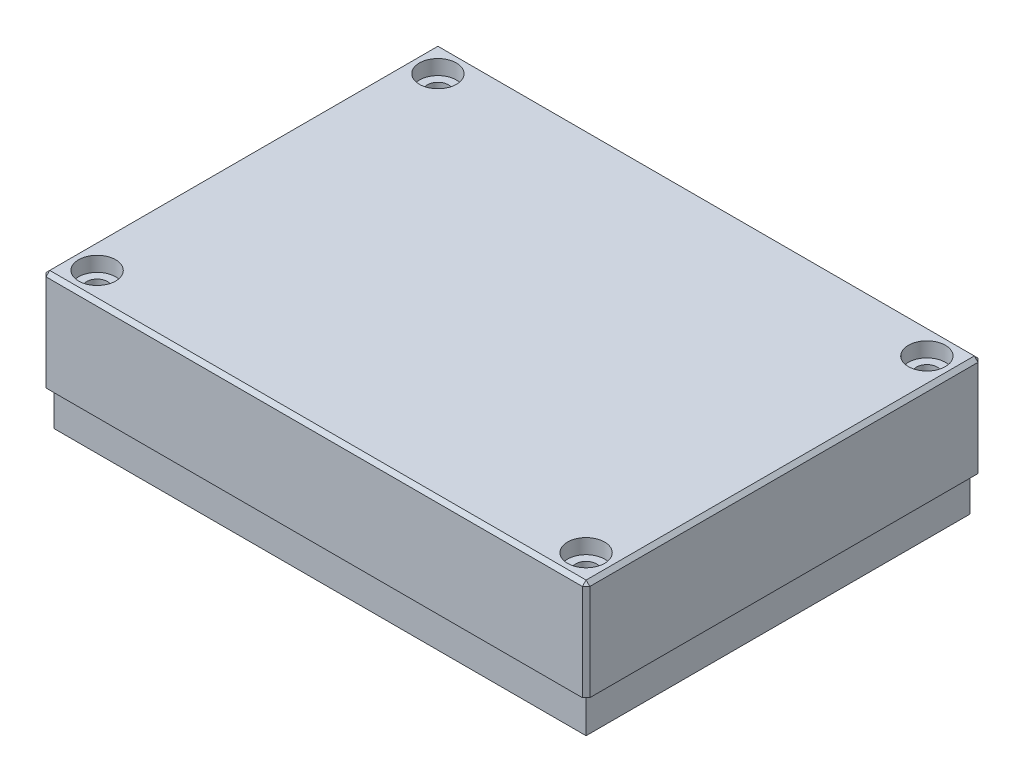
SolidWorks part; units mm, degrees
ref_plane "Спереди" through (0, 0, 0) normal (0, 0, 1) x (1, 0, 0)
ref_plane "Сверху" through (0, 0, 0) normal (0, 1, 0) x (1, 0, 0)
ref_plane "Справа" through (0, 0, 0) normal (1, 0, 0) x (0, 0, -1)
other "Configuration Table"
sketch "Эскиз1" plane through (0, 0, 0) normal (0, 1, 0) x (1, 0, 0)
  line L0 (-34.8, 24.8) -> (34.8, 24.8)
  line L1 (-35, -25) -> (35, -25) construction
  line L2 (-35, -25) -> (-35, 25) construction
  line L3 (-35, 25) -> (35, 25) construction
  line L4 (35, -25) -> (35, 25) construction
  line L5 (-35, -25) -> (35, 25) construction
  line L6 (-35, 25) -> (35, -25) construction
  line L7 (34.8, -24.8) -> (34.8, 24.8)
  line L8 (-34.8, -24.8) -> (34.8, -24.8)
  line L9 (-34.8, -24.8) -> (-34.8, 24.8)
  line L10 (-36.7, 26.7) -> (36.7, 26.7)
  line L11 (36.7, -26.7) -> (36.7, 26.7)
  line L12 (-36.7, -26.7) -> (36.7, -26.7)
  line L13 (-36.7, -26.7) -> (-36.7, 26.7)
  point P0 (0, 0)
  dimension "D1" = 70
  dimension "D2" = 50
  dimension "D3" = 0.2
  dimension "D4" = 1.9
extrude "Бобышка-Вытянуть1" add sketch "Эскиз1" against normal blind 17
sketch "Эскиз2" plane through (0, 0, 0) normal (0, 1, 0) x (1, 0, 0)
  line L1 (-36.7, 26.7) -> (36.7, 26.7)
  line L2 (-36.7, 26.7) -> (-36.7, -26.7)
  line L3 (-36.7, -26.7) -> (36.7, -26.7)
  line L4 (36.7, 26.7) -> (36.7, -26.7)
  line L5 (-36.7, 26.7) -> (36.7, -26.7) construction
  line L6 (-36.7, -26.7) -> (36.7, 26.7) construction
  point P4 (0, 0)
extrude "Бобышка-Вытянуть2" add sketch "Эскиз2" along normal blind 1.5
sketch "Эскиз3" plane through (0, 0, 0) normal (0, 1, 0) x (1, 0, 0)
  line L0 (-34.8, -24.8) -> (-34.8, 24.8) construction
  line L1 (-34.8, 24.8) -> (-30.3, 24.8)
  line L2 (-34.8, 24.8) -> (-34.8, 20.3)
  line L3 (-34.8, 20.3) -> (-30.3, 20.3)
  line L4 (-30.3, 24.8) -> (-30.3, 20.3)
  line L5 (-34.8, 24.8) -> (-30.3, 20.3) construction
  line L6 (-34.8, 20.3) -> (-30.3, 24.8) construction
  line L7 (-34.8, 24.8) -> (34.8, 24.8) construction
  line L8 (0, 0) -> (0, 17.8052) construction
  line L9 (0, 0) -> (16.7249, 0) construction
  line L10 (34.8, 20.3) -> (30.3, 24.8) construction
  line L11 (34.8, 24.8) -> (30.3, 20.3) construction
  line L12 (30.3, 24.8) -> (30.3, 20.3)
  line L13 (34.8, 20.3) -> (30.3, 20.3)
  line L14 (34.8, 24.8) -> (34.8, 20.3)
  line L15 (34.8, 24.8) -> (30.3, 24.8)
  line L16 (-34.8, -20.3) -> (-30.3, -24.8) construction
  line L17 (-34.8, -24.8) -> (-30.3, -20.3) construction
  line L18 (-30.3, -24.8) -> (-30.3, -20.3)
  line L19 (-34.8, -20.3) -> (-30.3, -20.3)
  line L20 (-34.8, -24.8) -> (-34.8, -20.3)
  line L21 (-34.8, -24.8) -> (-30.3, -24.8)
  line L22 (34.8, -24.8) -> (30.3, -20.3) construction
  line L23 (34.8, -20.3) -> (30.3, -24.8) construction
  line L24 (34.8, -24.8) -> (30.3, -24.8)
  line L25 (34.8, -24.8) -> (34.8, -20.3)
  line L26 (34.8, -20.3) -> (30.3, -20.3)
  line L27 (30.3, -24.8) -> (30.3, -20.3)
  point P4 (-32.55, 22.55)
  point P17 (32.55, 22.55)
  point P22 (-32.55, -22.55)
  point P27 (32.55, -22.55)
  dimension "D1" = 4.5
  dimension "D2" = 4.5
extrude "Бобышка-Вытянуть3" add sketch "Эскиз3" against normal through all
sketch "Эскиз9" plane through (0, 0, 0) normal (0, 1, 0) x (-1, 0, 0)
  circle A1 centre (-33, 23) radius 3.2527
  circle A2 centre (-33, -23) radius 3.2527
  circle A3 centre (33, -23) radius 3.2527
  circle A4 centre (33, 23) radius 3.2527
extrude "Бобышка-Вытянуть5" add sketch "Эскиз9" against normal blind 2
chamfer "Фаска1" distance 0.5 angle 45 8 edges at (0, 1.5, 26.7) (-36.7, -7.75, 26.7) (-36.7, 1.5, 0) (-36.7, -7.75, -26.7) (0, 1.5, -26.7) (36.7, -7.75, -26.7) (36.7, 1.5, 0) (36.7, -7.75, 26.7)
sketch "Эскиз6" plane through (0, -17, 0) normal (0, -1, 0) x (1, 0, 0)
  line L0 (36.7, 26.7) -> (36.7, -26.7) construction
  line L1 (-35.9, -25.9) -> (35.9, -25.9)
  line L2 (-35.9, -25.9) -> (-35.9, 25.9)
  line L3 (-35.9, 25.9) -> (35.9, 25.9)
  line L4 (35.9, -25.9) -> (35.9, 25.9)
  line L5 (-35.9, -25.9) -> (35.9, 25.9) construction
  line L6 (-35.9, 25.9) -> (35.9, -25.9) construction
  line L7 (-36.7, 26.7) -> (36.7, 26.7) construction
  point P0 (0, 0)
  dimension "D1" = 0.8
  dimension "D2" = 0.8
extrude "Вырез-Вытянуть3" cut sketch "Эскиз6" against normal blind 5 flip side to cut
sketch "Эскиз5" plane through (0, -17, 0) normal (0, -1, 0) x (1, 0, 0)
  line L0 (-35, 25) -> (35, 25) construction
  line L1 (-35, 25) -> (-35, -25) construction
  line L2 (0, 0) -> (0, -10.588) construction
  line L3 (0, 0) -> (10.9295, 0) construction
  circle A0 centre (-33, 23) radius 1.4
  circle A1 centre (33, 23) radius 1.4
  circle A2 centre (33, -23) radius 1.4
  circle A3 centre (-33, -23) radius 1.4
  dimension "D1" = 2
  dimension "D2" = 2
extrude "Вырез-Вытянуть2" cut sketch "Эскиз5" against normal through all
sketch "Эскиз7" plane through (0, 0, -26.7) normal (0, 0, -1) x (-1, 0, 0)
  line L0 (-24, -12) -> (-14, -12)
  line L7 (0, 0) -> (0, -21.4065) construction
  line L11 (16.5, -18.4) -> (16.5, -12)
  line L12 (6.5, -18.4) -> (16.5, -18.4)
  line L13 (6.5, -12) -> (6.5, -18.4)
  line L14 (6.5, -12) -> (16.5, -12)
  line L15 (-24, -18.4) -> (-14, -18.4)
  line L16 (-24, -12) -> (-24, -18.4)
  line L17 (-14, -18.4) -> (-14, -12)
  line L18 (-36.2, -12) -> (36.2, -12) construction
  dimension "D1" = 10
extrude "Вырез-Вытянуть4" cut sketch "Эскиз7" against normal up to next
sketch "Эскиз8" plane through (0, 1.5, 0) normal (0, 1, 0) x (1, 0, 0)
  circle A0 centre (-33, 23) radius 2.5
  circle A1 centre (33, 23) radius 2.5
  circle A2 centre (33, -23) radius 2.5
  circle A3 centre (-33, -23) radius 2.5
  dimension "D1" = 5
extrude "Вырез-Вытянуть5" cut sketch "Эскиз8" against normal blind 2
sketch "Эскиз10" plane through (-36.7, 0, 0) normal (-1, 0, 0) x (0, 0, 1)
  line L0 (26.7, 1) -> (26.7, -12) construction
  line L1 (6.95, 0) -> (16.45, 0)
  line L2 (6.95, 0) -> (6.95, -6.5)
  line L3 (6.95, -6.5) -> (16.45, -6.5)
  line L4 (16.45, 0) -> (16.45, -6.5)
  line L5 (6.95, 0) -> (16.45, -6.5) construction
  line L6 (6.95, -6.5) -> (16.45, 0) construction
  line L8 (26.7, 0) -> (-26.7, 0) construction
  point P4 (11.7, -3.25)
  dimension "D1" = 9.5
  dimension "D2" = 6.5
  dimension "D3" = 15
extrude "Вырез-Вытянуть6" cut sketch "Эскиз10" against normal blind 0.8
sketch "Эскиз11" plane through (-35.9, 0, 0) normal (-1, 0, 0) x (0, 0, 1)
  line L1 (7.6, -5.5) -> (15.8, -5.5)
  line L2 (7.6, -5.5) -> (7.6, -1)
  line L3 (7.6, -1) -> (15.8, -1)
  line L4 (15.8, -5.5) -> (15.8, -1)
  line L5 (7.6, -5.5) -> (15.8, -1) construction
  line L6 (7.6, -1) -> (15.8, -5.5) construction
  point P0 (11.7, -3.25)
  dimension "D1" = 4.5
  dimension "D2" = 8.2
extrude "Вырез-Вытянуть7" cut sketch "Эскиз11" against normal up to next
fillet "Скругление1" radius 1 8 edges at (-32.9917, 0, -19.7473) (-29.7473, 0, -22.9917) (-29.7473, 0, 22.9917) (-32.9917, 0, 19.7473) (32.9917, 0, 19.7473) (29.7473, 0, 22.9917) (29.7473, 0, -22.9917) (32.9917, 0, -19.7473)
